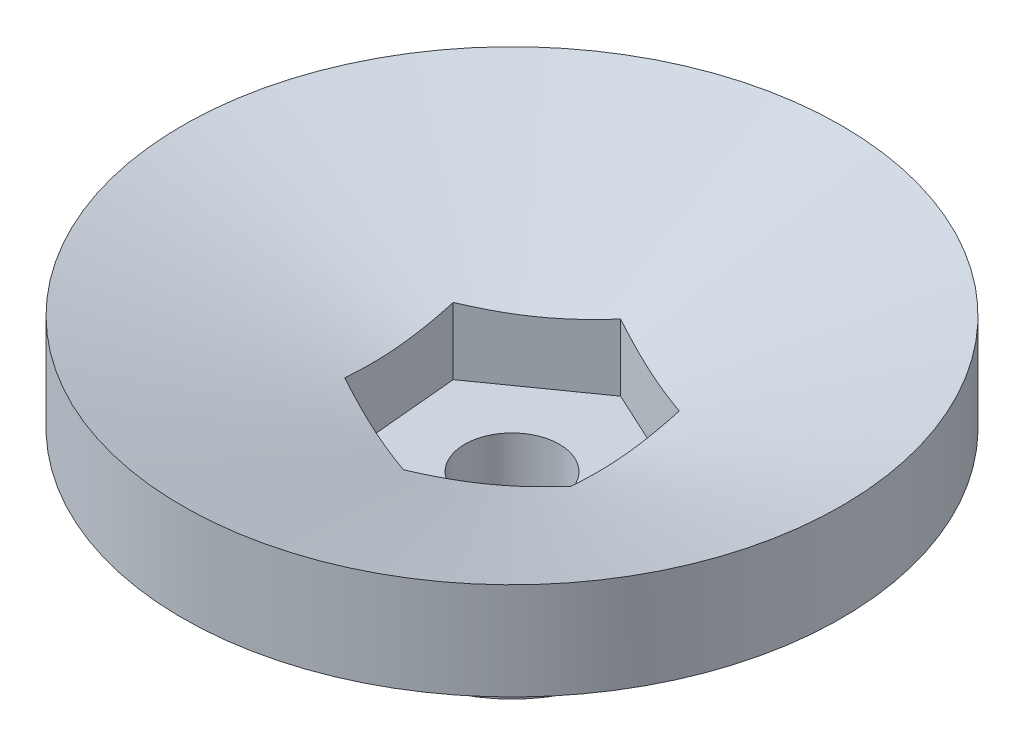
SolidWorks part; units mm, degrees
other "标注1"
sketch "草图7" plane through (28.1908, 18.774, -28.1908) normal (0.0889, 0.9358, -0.341) x (0.5595, -0.3302, -0.7602)
ref_plane "前视基准面" through (0, 0, 0) normal (0, 0, 1) x (1, 0, 0)
ref_plane "上视基准面" through (0, 0, 0) normal (0, 1, 0) x (1, 0, 0)
ref_plane "右视基准面" through (0, 0, 0) normal (1, 0, 0) x (0, 0, -1)
sketch "草图1" plane through (0, 0, 0) normal (0, 0, 1) x (1, 0, 0)
  line L0 (0, 0) -> (0, 8.4117)
  line L1 (0, 0) -> (28.5317, 9.2705)
  line L3 (28.5317, 9.2705) -> (28.5317, 17.6822)
  line L4 (28.5317, 17.6822) -> (0, 8.4117)
  dimension "D1" = 72
  dimension "D2" = 30
  dimension "D3" = 8
revolve "旋转2" add sketch "草图1" angle 360 about L0
sketch "草图2" plane through (0, 0, 0) normal (0, 0, 1) x (1, 0, 0)
  line L1 (-15, 5) -> (15, 5)
  line L2 (-15, 5) -> (-15, -5)
  line L3 (-15, -5) -> (15, -5)
  line L4 (15, 5) -> (15, -5)
  line L5 (-15, 5) -> (15, -5) construction
  line L6 (-15, -5) -> (15, 5) construction
  point P0 (0, 0)
  dimension "D1" = 10
  dimension "D2" = 30
extrude "切除-拉伸1" cut sketch "草图2" against normal through all and the other way through all
sketch "草图3" plane through (0, 5, 0) normal (0, -1, 0) x (1, 0, 0)
  circle A0 centre (0, 0) radius 3
  dimension "D1" = 6
extrude "切除-拉伸2" cut sketch "草图3" against normal through all
ref_plane "基准面1" through (0, 20, 0) normal (0, -1, 0) x (-1, 0, 0)
sketch "草图4" plane through (0, 20, 0) normal (0, -1, 0) x (-1, 0, 0)
  line L0 (0.0384, 3.4639) -> (-2.9806, 1.7652) construction
  line L1 (-2.9806, 1.7652) -> (-3.019, -1.6987) construction
  line L2 (0.0768, 6.9278) -> (-5.9613, 3.5304)
  line L3 (-5.9613, 3.5304) -> (-6.038, -3.3974)
  line L4 (-6.038, -3.3974) -> (-0.0768, -6.9278)
  line L5 (-0.0768, -6.9278) -> (5.9613, -3.5304)
  line L6 (5.9613, -3.5304) -> (6.038, 3.3974)
  line L7 (6.038, 3.3974) -> (0.0768, 6.9278)
  line L8 (-3.019, -1.6987) -> (-0.0384, -3.4639) construction
  line L9 (-0.0384, -3.4639) -> (2.9806, -1.7652) construction
  line L10 (2.9806, -1.7652) -> (3.019, 1.6987) construction
  line L11 (3.019, 1.6987) -> (0.0384, 3.4639) construction
  circle A0 centre (0, 0) radius 6 construction
  circle A1 centre (0, 0) radius 3
  dimension "D1" = 12
  dimension "D3" = 6
  dimension "D2" = 3
sketch "草图5" plane through (0, 5, 0) normal (0, -1, 0) x (1, 0, 0)
  circle A0 centre (0, 0) radius 10
  dimension "D1" = 20
extrude "凸台-拉伸1" add sketch "草图5" along normal blind 9
sketch "草图6" plane through (0, 5, 0) normal (0, 1, 0) x (1, 0, 0)
  circle A0 centre (0, 0) radius 4.1
  dimension "D1" = 8.2
extrude "切除-拉伸7" cut sketch "草图6" against normal through all and the other way through all
fillet "圆角2" radius 5 1 edges at (0, 5, 10)
ref_plane "基准面2" through (0, 10, 0) normal (0, -1, 0) x (-1, 0, 0)
sketch "草图9" plane through (0, 10, 0) normal (0, -1, 0) x (-1, 0, 0)
  line L1 (8.4857, -5.9994) -> (9.4385, 4.3491)
  line L2 (9.4385, 4.3491) -> (0.9528, 10.3485)
  line L3 (0.9528, 10.3485) -> (-8.4857, 5.9994)
  line L4 (-8.4857, 5.9994) -> (-9.4385, -4.3491)
  line L5 (-9.4385, -4.3491) -> (-0.9528, -10.3485)
  line L6 (-0.9528, -10.3485) -> (8.4857, -5.9994)
  circle A0 centre (0, 0) radius 9 construction
  dimension "D1" = 18
extrude "切除-拉伸8" cut sketch "草图9" against normal blind 12 and the other way blind 4
